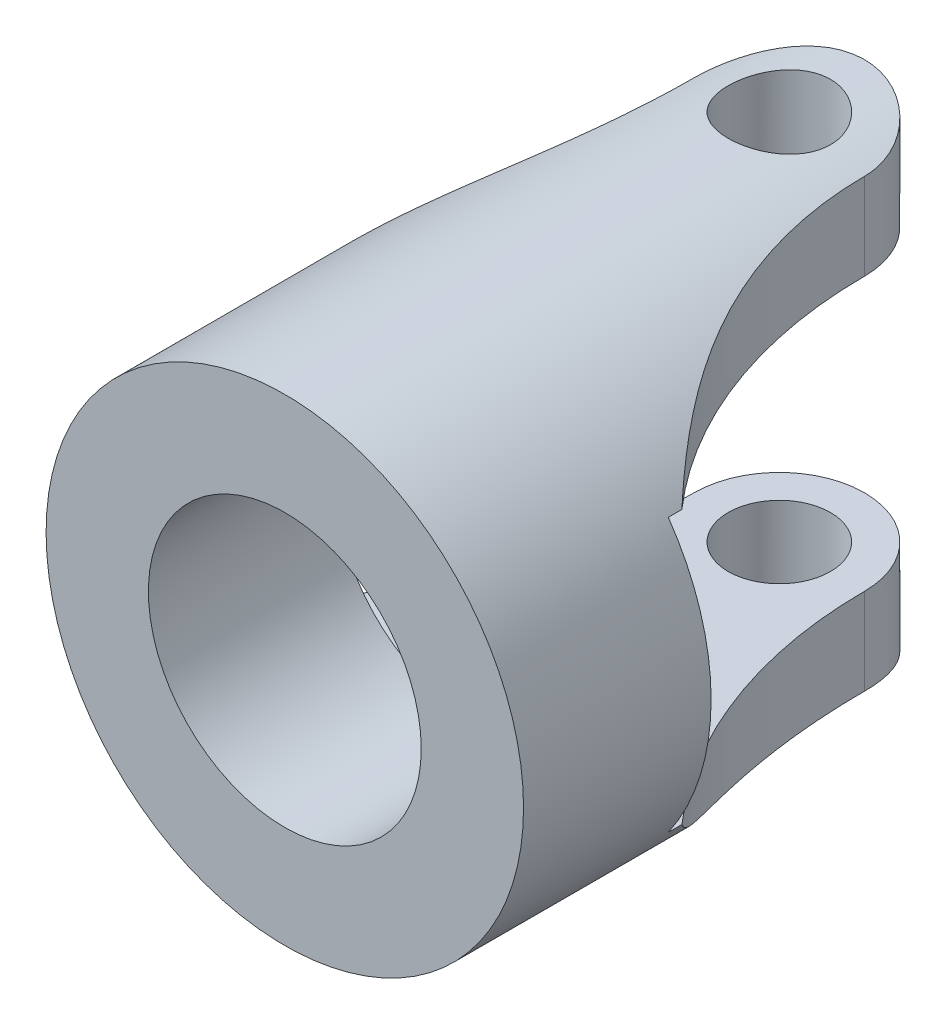
SolidWorks part; units mm, degrees
ref_plane "Front Plane" through (0, 0, 0) normal (0, 0, 1) x (1, 0, 0)
ref_plane "Top Plane" through (0, 0, 0) normal (0, 1, 0) x (1, 0, 0)
ref_plane "Right Plane" through (0, 0, 0) normal (1, 0, 0) x (0, 0, -1)
sketch "Sketch1" plane through (0, 0, 0) normal (0, 0, 1) x (1, 0, 0)
  circle A0 centre (0, 0) radius 4
  circle A1 centre (0, 0) radius 7
  dimension "D1" = 8
  dimension "D2" = 14
extrude "Boss-Extrude1" add sketch "Sketch1" along normal blind 17
sketch "Sketch2" plane through (0, 0, 0) normal (0, 1, 0) x (1, 0, 0)
  line L0 (0, 0) -> (0, -17) construction
  line L1 (-7, -17) -> (7, -17) construction
  line L2 (-7, -11.5) -> (7, -11.5) construction
  line L3 (-7, 0) -> (-7, -17) construction
  line L4 (7, -17) -> (7, 0) construction
  line L5 (-7, -11.5) -> (-7, 0)
  line L6 (-7, 0) -> (0, 1)
  line L7 (0, 1) -> (7, 0)
  line L8 (7, 0) -> (-7, 0) construction
  line L9 (7, 0) -> (7, -11.5)
  line L10 (-7, -11.5) -> (-6.1094, -11.5)
  line L11 (6.1094, -11.5) -> (7, -11.5)
  circle A0 centre (0, -2.5) radius 1.5
  arc A1 (2.5, -2.5) -> (-2.5, -2.5) centre (0, -2.5) ccw
  arc A4 (-6.1094, -11.5) -> (-2.5, -2.5) centre (-15.5253, -2.5) ccw
  arc A5 (6.1094, -11.5) -> (2.5, -2.5) centre (15.5253, -2.5) cw
  dimension "D2" = 3
  dimension "D3" = 2.5
  dimension "D1" = 5.5
  dimension "D5" = 1
  dimension "D6" = 0.8906
extrude "Cut-Extrude1" cut sketch "Sketch2" against normal through all both and the other way through all contours A0 | L9 L11 A5 A1 A4 L10 L5 L6 L7
sketch "Sketch3" plane through (0, 0, 0) normal (1, 0, 0) x (0, 0, -1)
  line L0 (-11.5, 7) -> (-11.5, -7) construction
  line L1 (-4, 7) -> (-17, 7) construction
  line L2 (-17, -7) -> (-4, -7) construction
  line L3 (-17, 7) -> (-17, -7) construction
  line L4 (0, 4) -> (-11.5, 4)
  line L5 (0, -4) -> (-11.5, -4)
  line L6 (-11.5, -4) -> (-11.5, 4)
  line L8 (0, 4) -> (0, -4)
  spline S0 degree 2 poles (0, 4) (-1.404, 3.1225) (-2.5, 3.1225) knots 0 0 0 0.3245 0.3245 0.3245 weights 0.0015 0.002311 0.003122 construction
  point P14 (0, 3.9974)
  point P15 (-13, 4)
  point P18 (0, -4)
  dimension "D1" = 5.5
extrude "Cut-Extrude2" cut sketch "Sketch3" against normal through all both and the other way through all
sketch "Sketch8" plane through (0, 0, 0) normal (0, 1, 0) x (1, 0, 0)
  line L0 (0, -2.5) -> (0, -17) construction
  line L1 (-7, -17) -> (7, -17) construction
